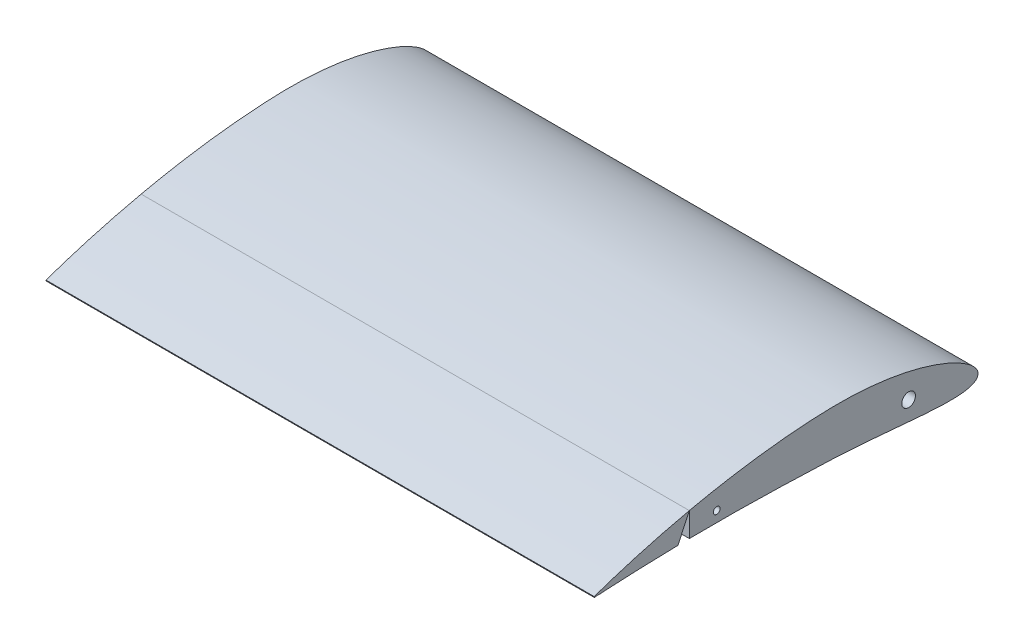
SolidWorks part; units mm, degrees
material "Thornel Mat VMA Foam Core"
ref_plane "Front Plane" through (0, 0, 0) normal (0, 0, 1) x (1, 0, 0)
ref_plane "Top Plane" through (0, 0, 0) normal (0, 1, 0) x (1, 0, 0)
ref_plane "Right Plane" through (0, 0, 0) normal (1, 0, 0) x (0, 0, -1)
curve "Curve1"
  spline degree 3 poles (0, 0.0012, 1.0003) (0, 0.0015, 0.9994) (0, 0.0028, 0.9958) (0, 0.0055, 0.9879) (0, 0.0099, 0.9747) (0, 0.0159, 0.9565) (0, 0.0233, 0.9333) (0, 0.0318, 0.9054) (0, 0.0411, 0.8731) (0, 0.051, 0.8366) (0, 0.0612, 0.7964) (0, 0.0713, 0.7528) (0, 0.0811, 0.7063) (0, 0.0903, 0.6574) (0, 0.0985, 0.6067) (0, 0.1057, 0.5546) (0, 0.1115, 0.5018) (0, 0.1158, 0.4488) (0, 0.1186, 0.3959) (0, 0.1189, 0.3436) (0, 0.1164, 0.2927) (0, 0.1112, 0.2442) (0, 0.1037, 0.1988) (0, 0.0942, 0.157) (0, 0.0831, 0.1194) (0, 0.0711, 0.0865) (0, 0.0584, 0.0585) (0, 0.0457, 0.0357) (0, 0.0334, 0.0184) (0, 0.0218, 0.0064) (0, 0.0108, -0.0005) (0, -0.0003, -0.0011) (0, -0.0092, 0.0055) (0, -0.0148, 0.017) (0, -0.0185, 0.0329) (0, -0.0204, 0.0533) (0, -0.0208, 0.0781) (0, -0.0198, 0.107) (0, -0.0176, 0.1398) (0, -0.0147, 0.176) (0, -0.0111, 0.2153) (0, -0.0074, 0.2574) (0, -0.0037, 0.3019) (0, -0.0005, 0.3484) (0, 0.002, 0.397) (0, 0.0037, 0.4471) (0, 0.0055, 0.4983) (0, 0.0069, 0.5496) (0, 0.0079, 0.6006) (0, 0.0085, 0.6505) (0, 0.0086, 0.699) (0, 0.0083, 0.7455) (0, 0.0076, 0.7894) (0, 0.0065, 0.8302) (0, 0.0053, 0.8675) (0, 0.0039, 0.9007) (0, 0.0027, 0.9296) (0, 0.0013, 0.9539) (0, 0.0006, 0.9727) (0, -0.0011, 0.9872) (0, 0, 0.9944) (0, -0.002, 0.9999) (0, -0.0005, 1) (0, 0, 1) knots 0 0 0 0 0.001372 0.005465 0.012235 0.021602 0.033461 0.047671 0.064081 0.082496 0.102719 0.124527 0.147676 0.171913 0.196978 0.222597 0.248497 0.274385 0.300041 0.32569 0.350525 0.37428 0.396711 0.417577 0.436654 0.453744 0.46868 0.481329 0.491631 0.499616 0.505546 0.510185 0.514824 0.520702 0.528516 0.538466 0.550543 0.564643 0.580638 0.598345 0.617584 0.638174 0.659922 0.682632 0.706121 0.730727 0.7557 0.780732 0.805564 0.829932 0.85357 0.876213 0.89761 0.917519 0.935698 0.951943 0.966047 0.97784 0.987174 0.993932 0.998018 0.999386 1 1 1 1
sketch "Sketch1" plane through (0, 0, 0) normal (1, 0, 0) x (0, 0, -1)
  line L0 (-354.7873, -0.0303) -> (-354.8762, 0.4104)
  line L1 (-354.7873, -0.0303) -> (0.8093, 1.5275) construction
  line L2 (0.8093, 1.5275) -> (0.7921, 5.4415) construction
  spline S1 degree 3 poles (-354.8762, 0.4104) (-354.5599, 0.5194) (-353.2997, 0.9536) (-350.4787, 1.9271) (-345.801, 3.4978) (-336.0241, 6.7216) (-319.6545, 11.7989) (-300.5983, 17.1306) (-282.4229, 21.7243) (-261.1758, 26.6516) (-238.6223, 31.1455) (-208.7748, 36.0048) (-183.9617, 39.0905) (-158.9023, 41.1132) (-140.0967, 42.1114) (-121.5167, 42.2289) (-103.4222, 41.3211) (-86.1884, 39.4787) (-70.0435, 36.8105) (-55.1998, 33.4329) (-41.8434, 29.5109) (-30.1305, 25.2201) (-20.187, 20.7343) (-12.1072, 16.2263) (-5.9269, 11.8553) (-1.6792, 7.7165) (0.7658, 3.7968) (0.9875, -0.1483) (-1.3511, -3.3089) (-5.4508, -5.2881) (-11.0873, -6.5875) (-18.3491, -7.2685) (-27.1638, -7.4049) (-37.4471, -7.0538) (-49.0831, -6.3019) (-61.9524, -5.238) (-75.9299, -3.9839) (-96.4067, -2.1536) (-117.9372, -0.4584) (-140.4848, 0.6745) (-158.2965, 1.2867) (-176.4839, 1.9179) (-200.672, 2.5862) (-224.5411, 2.9791) (-247.8302, 3.0285) (-264.3373, 2.9074) (-279.9331, 2.6564) (-294.438, 2.2829) (-307.6819, 1.8521) (-319.5134, 1.3711) (-329.7674, 0.9129) (-338.3889, 0.4268) (-345.077, 0.1915) (-350.2276, -0.4064) (-352.7802, -0.0354) (-354.7446, -0.7581) (-354.7772, -0.2025) (-354.7873, -0.0303) knots 0 0 0 0 0.001372 0.005465 0.012235 0.021602 0.047671 0.082496 0.102719 0.124527 0.171913 0.196978 0.248497 0.274385 0.300041 0.32569 0.350525 0.37428 0.396711 0.417577 0.436654 0.453744 0.46868 0.481329 0.491631 0.499616 0.505546 0.510185 0.514824 0.520702 0.528516 0.538466 0.550543 0.564643 0.580638 0.598345 0.617584 0.638174 0.682632 0.706121 0.730727 0.7557 0.780732 0.829932 0.85357 0.876213 0.89761 0.917519 0.935698 0.951943 0.966047 0.97784 0.987174 0.993932 0.998018 0.999386 1 1 1 1
  dimension "D1" = 355.6
extrude "Boss-Extrude1" add sketch "Sketch1" along normal blind 254 and the other way blind 254
sketch "Sketch2" plane through (-254, 0, 0) normal (-1, 0, 0) x (0, 0, 1)
  line L0 (266.7, 0) -> (266.7, 78.4574) construction
  line L1 (195.725, 0) -> (-195.725, 0) construction
  line L2 (0, -27.2986) -> (0, 27.2986) construction
  line L3 (266.7, 25.311) -> (266.7, 2.0657)
  line L4 (266.7, 25.311) -> (277.5394, 2.0657)
  line L5 (277.5394, 2.0657) -> (266.7, 2.0657)
  spline S0 degree 3 poles (354.7873, -0.0303) (354.7772, -0.2025) (354.7446, -0.7581) (352.7802, -0.0354) (350.2276, -0.4064) (345.077, 0.1915) (338.3889, 0.4268) (329.7674, 0.9129) (319.5134, 1.3711) (307.6819, 1.8521) (294.438, 2.2829) (279.9331, 2.6564) (264.3373, 2.9074) (247.8302, 3.0285) (224.5411, 2.9791) (200.672, 2.5862) (176.4839, 1.9179) (158.2965, 1.2867) (140.4848, 0.6745) (117.9372, -0.4584) (96.4067, -2.1536) (75.9299, -3.9839) (61.9524, -5.238) (49.0831, -6.3019) (37.4471, -7.0538) (27.1638, -7.4049) (18.3491, -7.2685) (11.0873, -6.5875) (5.4508, -5.2881) (1.3511, -3.3089) (-0.9875, -0.1483) (-0.7658, 3.7968) (1.6792, 7.7165) (5.9269, 11.8553) (12.1072, 16.2263) (20.187, 20.7343) (30.1305, 25.2201) (41.8434, 29.5109) (55.1998, 33.4329) (70.0435, 36.8105) (86.1884, 39.4787) (103.4222, 41.3211) (121.5167, 42.2289) (140.0967, 42.1114) (158.9023, 41.1132) (183.9617, 39.0905) (208.7748, 36.0048) (238.6223, 31.1455) (261.1758, 26.6516) (282.4229, 21.7243) (300.5983, 17.1306) (319.6545, 11.7989) (336.0241, 6.7216) (345.801, 3.4978) (350.4787, 1.9271) (353.2997, 0.9536) (354.5599, 0.5194) (354.8762, 0.4104) knots 0 0 0 0 0.000614 0.001982 0.006068 0.012826 0.02216 0.033953 0.048057 0.064302 0.082481 0.10239 0.123787 0.14643 0.170068 0.219268 0.2443 0.269273 0.293879 0.317368 0.361826 0.382416 0.401655 0.419362 0.435357 0.449457 0.461534 0.471484 0.479298 0.485176 0.489815 0.494454 0.500384 0.508369 0.518671 0.53132 0.546256 0.563346 0.582423 0.603289 0.62572 0.649475 0.67431 0.699959 0.725615 0.751503 0.803022 0.828087 0.875473 0.897281 0.917504 0.952329 0.978398 0.987765 0.994535 0.998628 1 1 1 1 construction
  dimension "D1" = 266.7
  dimension "D2" = 25
extrude "Cut-Extrude1" cut sketch "Sketch2" against normal up to next
sketch "Sketch4" plane through (-254, 0, 0) normal (-1, 0, 0) x (0, 0, 1)
  line L0 (195.725, 0) -> (-195.725, 0) construction
  line L1 (0, -27.2986) -> (0, 27.2986) construction
  circle A0 centre (63.5, 12.7) radius 6.35
  dimension "D1" = 12.7
  dimension "D2" = 12.7
  dimension "D3" = 63.5
extrude "Cut-Extrude2" cut sketch "Sketch4" against normal blind 101.6
mirror "Mirror1" about plane through (0, 0, 0) normal (1, 0, 0) of "Cut-Extrude2"
sketch "Sketch5" plane through (-254, 0, 0) normal (-1, 0, 0) x (0, 0, 1)
  line L0 (195.725, 0) -> (-195.725, 0) construction
  line L1 (0, -27.2986) -> (0, 27.2986) construction
  circle A0 centre (241.3, 12.7) radius 3.175
  dimension "D1" = 6.35
  dimension "D2" = 12.7
  dimension "D3" = 241.3
extrude "Cut-Extrude3" cut sketch "Sketch5" against normal blind 127
mirror "Mirror2" about plane through (0, 0, 0) normal (1, 0, 0) of "Cut-Extrude3"
